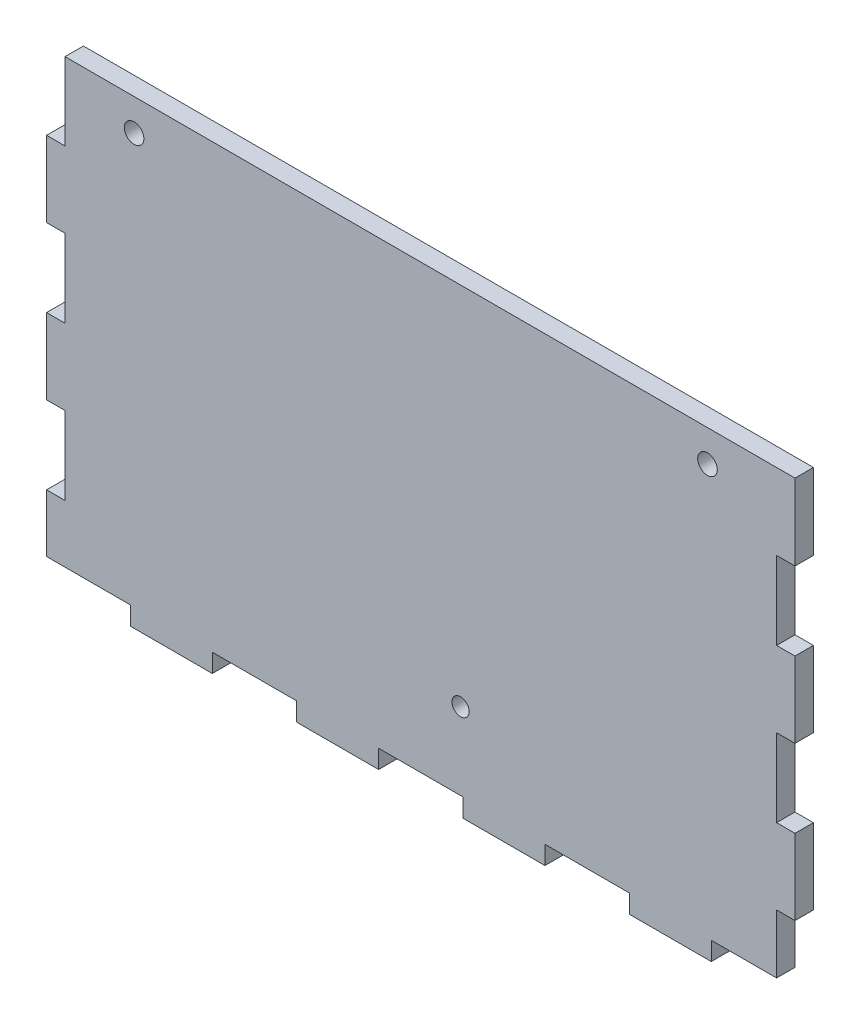
SolidWorks part; units mm, degrees
ref_plane "Front Plane" through (0, 0, 0) normal (0, 0, 1) x (1, 0, 0)
ref_plane "Top Plane" through (0, 0, 0) normal (0, 1, 0) x (1, 0, 0)
ref_plane "Right Plane" through (0, 0, 0) normal (1, 0, 0) x (0, 0, -1)
sketch "Sketch1" plane through (0, 0, 0) normal (0, 0, 1) x (1, 0, 0)
  line L1 (0, 0) -> (130, 0)
  line L2 (0, 0) -> (0, 80)
  line L3 (0, 80) -> (130, 80)
  line L4 (130, 0) -> (130, 80)
  dimension "D1" = 130
  dimension "D2" = 80
extrude "Boss-Extrude1" add sketch "Sketch1" along normal blind 3.2
sketch "Sketch2" plane through (0, 0, 3.2) normal (0, 0, 1) x (1, 0, 0)
  line L61 (14.4444, 3.2) -> (28.8889, 3.2) construction
  line L62 (0, 0) -> (14.4444, 0)
  line L67 (0, 0) -> (0, 3.2)
  line L72 (0, 3.2) -> (14.4444, 3.2)
  line L77 (14.4444, 0) -> (14.4444, 3.2)
  line L97 (28.8889, 0) -> (28.8889, 3.2)
  line L98 (28.8889, 0) -> (43.3333, 0)
  line L107 (43.3333, 0) -> (43.3333, 3.2)
  line L115 (28.8889, 3.2) -> (43.3333, 3.2)
  line L117 (43.3333, 3.2) -> (57.7778, 3.2) construction
  line L123 (57.7778, 0) -> (57.7778, 3.2)
  line L128 (57.7778, 0) -> (72.2222, 0)
  line L129 (72.2222, 0) -> (72.2222, 3.2)
  line L131 (57.7778, 3.2) -> (72.2222, 3.2)
  line L132 (72.2222, 3.2) -> (86.6667, 3.2) construction
  line L133 (86.6667, 0) -> (86.6667, 3.2)
  line L134 (86.6667, 0) -> (101.1111, 0)
  line L135 (101.1111, 0) -> (101.1111, 3.2)
  line L136 (86.6667, 3.2) -> (101.1111, 3.2)
  line L137 (101.1111, 3.2) -> (115.5556, 3.2) construction
  line L138 (115.5556, 0) -> (115.5556, 3.2)
  line L139 (115.5556, 0) -> (130, 0)
  line L142 (130, 0) -> (130, 80) construction
  line L143 (0, 80) -> (0, 0) construction
  line L144 (0, 13.3333) -> (3.2, 13.3333)
  line L145 (0, 13.3333) -> (0, 26.6667)
  line L146 (130, 3.2) -> (144.4444, 3.2) construction
  line L147 (0, 26.6667) -> (3.2, 26.6667)
  line L148 (3.2, 13.3333) -> (3.2, 26.6667)
  line L149 (3.2, 13.3333) -> (3.2, 0) construction
  line L150 (0, 40) -> (0, 53.3333)
  line L151 (0, 40) -> (3.2, 40)
  line L152 (3.2, 40) -> (3.2, 53.3333)
  line L153 (0, 53.3333) -> (3.2, 53.3333)
  line L154 (3.2, 40) -> (3.2, 26.6667) construction
  line L155 (0, 66.6667) -> (0, 80)
  line L156 (0, 66.6667) -> (3.2, 66.6667)
  line L157 (3.2, 66.6667) -> (3.2, 80)
  line L158 (0, 80) -> (3.2, 80)
  line L159 (3.2, 66.6667) -> (3.2, 53.3333) construction
  line L160 (130, 80) -> (0, 80) construction
  line L161 (126.8, 80) -> (126.8, 66.6667) construction
  line L162 (126.8, 40) -> (126.8, 26.6667)
  line L163 (126.8, 66.6667) -> (130, 66.6667)
  line L164 (126.8, 66.6667) -> (126.8, 53.3333)
  line L165 (126.8, 53.3333) -> (130, 53.3333)
  line L166 (130, 66.6667) -> (130, 53.3333)
  line L167 (126.8, 40) -> (130, 40)
  line L168 (130, 40) -> (130, 26.6667)
  line L169 (126.8, 26.6667) -> (130, 26.6667)
  line L170 (126.8, 53.3333) -> (126.8, 40) construction
  line L172 (126.8, 13.3333) -> (130, 13.3333)
  line L173 (130, 13.3333) -> (130, 0)
  line L175 (126.8, 26.6667) -> (126.8, 13.3333) construction
  line L183 (115.5556, 3.2) -> (130, 3.2) [skipped]
  line L184 (130, 0) -> (130, 3.2) [skipped]
  line L185 (126.8, 13.3333) -> (126.8, 3.2)
  line L186 (126.8, 3.2) -> (115.5556, 3.2)
  line L187 (126.8, 0) -> (130, 0) [skipped]
  line L188 (126.8, 13.3333) -> (126.8, 0) [skipped]
  dimension "D2" = 3.2
  dimension "D4" = 3.2
  dimension "D6" = 3.2
  dimension "D1" = 5
  dimension "D3" = 3
  dimension "D5" = 3
extrude "Cut-Extrude1" cut sketch "Sketch2" against normal through all
other "Move Face1" flip direction yes face at (128.4, 53.3333, 1.6) face at (128.4, 26.6667, 1.6) face at (128.4, 13.3333, 1.6) face at (128.4, 40, 1.6) face at (128.4, 66.6667, 1.6) face at (115.5556, 1.6, 1.6) face at (86.6667, 1.6, 1.6) face at (57.7778, 1.6, 1.6) face at (28.8889, 1.6, 1.6) face at (14.4444, 1.6, 1.6) face at (43.3333, 1.6, 1.6) face at (72.2222, 1.6, 1.6) face at (101.1111, 1.6, 1.6) face at (1.6, 26.6667, 1.6) face at (1.6, 13.3333, 1.6) face at (1.6, 40, 1.6) face at (1.6, 53.3333, 1.6) face at (1.6, 66.6667, 1.6) offset 0.1 parameters "D1"=0.1
sketch "Sketch3" plane through (0, 0, 3.2) normal (0, 0, 1) x (1, 0, 0)
  line L0 (0, 66.5667) -> (0, 53.4333) construction
  line L1 (130, 80) -> (3.2, 80) construction
  line L2 (0, 66.5667) -> (130, 66.7667) construction
  line L3 (65, 66.6667) -> (65, 50066.6667) construction
  circle A0 centre (15.2, 74.5) radius 1.7
  circle A1 centre (114.8, 74.5) radius 1.7
  point P10 (65, 66.6667)
  dimension "D1" = 3.4
  dimension "D2" = 15.2
  dimension "D3" = 5.5
extrude "Cut-Extrude2" cut sketch "Sketch3" against normal up to next
sketch "Sketch4" plane through (0, 0, 0) normal (0, 0, -1) x (-1, 0, 0)
  line L0 (-130, 13.4333) -> (-130, 26.5667) construction
  line L4 (-72.3222, 3.2) -> (-57.6778, 3.2) construction
  circle A0 centre (-71.91, 16.56) radius 1.5
  dimension "D2" = 3
  dimension "D1" = 58.09
  dimension "D3" = 13.36
extrude "Cut-Extrude3" cut sketch "Sketch4" against normal up to next
equation "\"wall_thickness\"= 3.2mm"
equation "\"D1@Boss-Extrude1\"=\"wall_thickness\""
equation "\"slot_width_tolerance\"= 0.1mm"
equation "\"slot_depth\"= 3.2mm"
equation "\"D2@Sketch2\"=\"slot_depth\""
equation "\"D4@Sketch2\"=\"slot_depth\""
equation "\"D6@Sketch2\"=\"slot_depth\""
equation "\"D2@Sketch3\"=12.00mm+\"slot_depth\""
